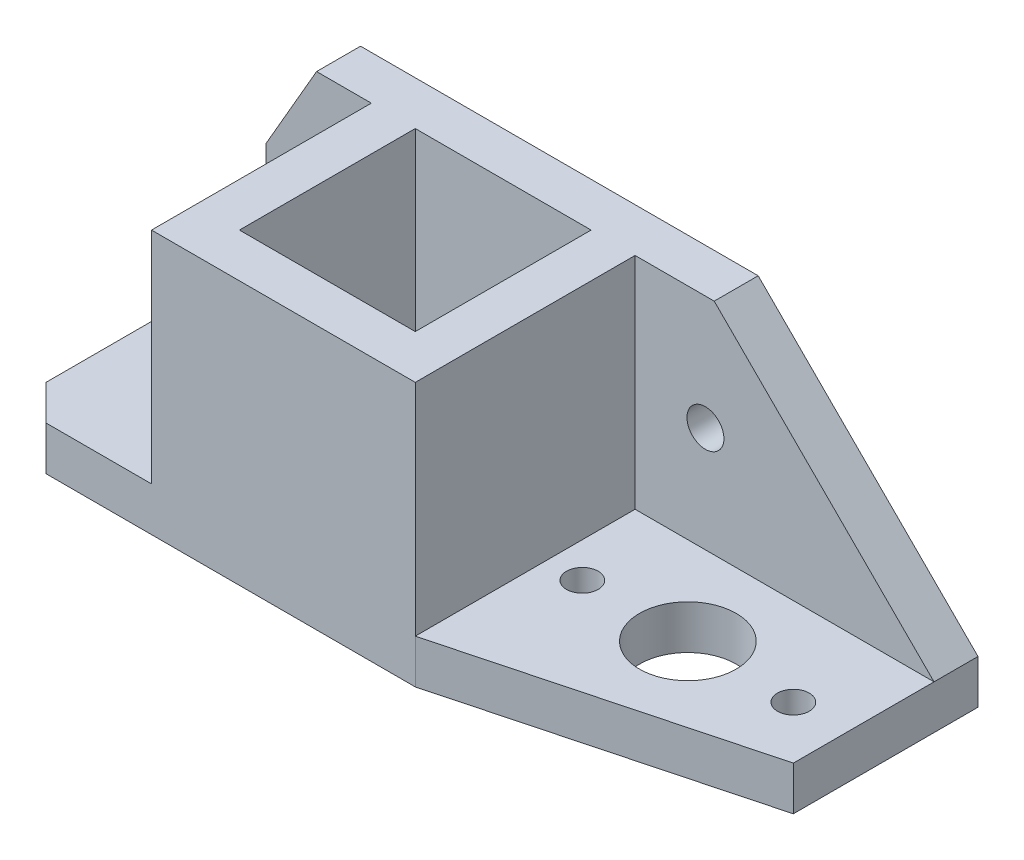
SolidWorks part; units mm, degrees
ref_plane "Front Plane" through (0, 0, 0) normal (0, 0, 1) x (1, 0, 0)
ref_plane "Top Plane" through (0, 0, 0) normal (0, 1, 0) x (1, 0, 0)
ref_plane "Right Plane" through (0, 0, 0) normal (1, 0, 0) x (0, 0, -1)
sketch "Sketch1" plane through (0, 0, 0) normal (0, 1, 0) x (1, 0, 0)
  line L1 (-15, 15) -> (15, 15)
  line L2 (-15, 15) -> (-15, -15)
  line L3 (-15, -15) -> (15, -15)
  line L4 (15, 15) -> (15, -15)
  dimension "D1" = 30
  dimension "D2" = 30
  dimension "D3" = 15
  dimension "D4" = 15
extrude "Boss-Extrude1" add sketch "Sketch1" along normal blind 30
sketch "Sketch2" plane through (0, 30, 0) normal (0, 1, 0) x (1, 0, 0)
  line L0 (-15, 15) -> (-15, -15) construction
  line L1 (-10, 10) -> (10, 10)
  line L2 (-10, 10) -> (-10, -10)
  line L3 (-10, -10) -> (10, -10)
  line L4 (10, 10) -> (10, -10)
  line L5 (15, 15) -> (-15, 15) construction
  dimension "D1" = 20
  dimension "D2" = 20
  dimension "D3" = 5
  dimension "D4" = 5
extrude "Cut-Extrude1" cut sketch "Sketch2" against normal through all
sketch "Sketch3" plane through (15, 0, 0) normal (1, 0, 0) x (0, 0, -1)
  line L0 (15, 30) -> (15, 0) construction
  line L1 (-15, 0) -> (15, 0)
  line L2 (-15, 0) -> (-15, 5)
  line L3 (-15, 5) -> (15, 5)
  line L4 (15, 0) -> (15, 5)
  dimension "D1" = 5
extrude "Boss-Extrude2" add sketch "Sketch3" along normal blind 40
sketch "Sketch4" plane through (0, 0, 0) normal (0, -1, 0) x (1, 0, 0)
  line L0 (10, 10) -> (10, -10) construction
  line L1 (-10, 10) -> (10, 10) construction
  circle A0 centre (31, 0) radius 5.5
  circle A1 centre (19, 0) radius 1.8
  circle A2 centre (43, 0) radius 1.8
  dimension "D2" = 11
  dimension "D3" = 3.6
  dimension "D4" = 3.6
  dimension "D1" = 21
  dimension "D5" = 10
  dimension "D6" = 10
  dimension "D7" = 10
  dimension "D8" = 12
  dimension "D9" = 12
extrude "Cut-Extrude2" cut sketch "Sketch4" against normal through all
sketch "Sketch7" plane through (0, 5, 0) normal (0, 1, 0) x (1, 0, 0)
  line L0 (15, -15) -> (49, -6)
  line L1 (49, -6) -> (49, 15)
  line L2 (55, 15) -> (15, 15) construction
  line L3 (49, 15) -> (55, 15)
  line L4 (55, 15) -> (55, -15)
  line L5 (55, 15) -> (55, -15) construction
  line L6 (55, -15) -> (15, -15) construction
  line L7 (55, -15) -> (15, -15)
  circle A0 centre (43, 0) radius 1.8 construction
  dimension "D1" = 6
  dimension "D2" = 6
extrude "Cut-Extrude3" cut sketch "Sketch7" against normal through all
sketch "Sketch5" plane through (15, 0, 0) normal (1, 0, 0) x (0, 0, -1)
  line L0 (15, 5) -> (-15, 5) construction
  line L1 (15, 30) -> (10, 30)
  line L2 (15, 30) -> (15, 5)
  line L3 (15, 5) -> (10, 5)
  line L4 (10, 30) -> (10, 5)
  dimension "D1" = 5
extrude "Boss-Extrude4" add sketch "Sketch5" along normal up to surface (34 mm away) up to face at (49, 2.5, -4.5)
chamfer "Chamfer1" distance 25 angle 45 1 edges at (49, 30, -12.5)
sketch "Sketch8" plane through (0, 0, -10) normal (0, 0, 1) x (1, 0, 0)
  line L0 (15, 30) -> (15, 5) construction
  line L1 (24, 30) -> (15, 30) construction
  circle A0 centre (23, 17) radius 2.1
  dimension "D1" = 4.2
  dimension "D2" = 8
  dimension "D3" = 13
extrude "Cut-Extrude4" cut sketch "Sketch8" against normal through all
sketch "Sketch9" plane through (-15, 0, 0) normal (-1, 0, 0) x (0, 0, 1)
  line L0 (-15, 0) -> (15, 0) construction
  line L1 (-15, 30) -> (-10, 30)
  line L2 (-15, 30) -> (-15, 0)
  line L3 (-15, 0) -> (-10, 0)
  line L4 (-10, 30) -> (-10, 0)
  dimension "D1" = 5
extrude "Boss-Extrude5" add sketch "Sketch9" along normal blind 12
chamfer "Chamfer2" distance 10 angle 30 1 edges at (-27, 30, -12.5) first distance on face at (-27, 15, -12.5)
sketch "Sketch10" plane through (0, 0, -10) normal (0, 0, 1) x (1, 0, 0)
  line L0 (-21.2265, 30) -> (-15, 30) construction
  line L1 (-15, 0) -> (-15, 30) construction
  circle A0 centre (-21, 17) radius 2.1
  dimension "D1" = 4.2
  dimension "D2" = 13
  dimension "D3" = 6
extrude "Cut-Extrude5" cut sketch "Sketch10" against normal through all
sketch "Sketch11" plane through (-15, 0, 0) normal (-1, 0, 0) x (0, 0, 1)
  line L0 (-10, 0) -> (-10, 30) construction
  line L1 (15, 0) -> (-10, 0)
  line L2 (15, 0) -> (15, 5)
  line L3 (15, 5) -> (-10, 5)
  line L4 (-10, 0) -> (-10, 5)
  dimension "D1" = 5
extrude "Boss-Extrude6" add sketch "Sketch11" along normal blind 16
chamfer "Chamfer3" distance 4 angle 45 2 edges at (-31, 2.5, 15) (-31, 2.5, -10)
sketch "Sketch12" plane through (0, 5, 0) normal (0, 1, 0) x (1, 0, 0)
  line L0 (-27, 10) -> (-15, 10) construction
  line L1 (-31, -11) -> (-31, 6) construction
  circle A0 centre (-25, 0) radius 1.8
  dimension "D1" = 3.6
  dimension "D2" = 10
  dimension "D3" = 6
extrude "Cut-Extrude6" cut sketch "Sketch12" against normal through all
sketch "Sketch13" plane through (0, 5, 0) normal (0, 1, 0) x (1, 0, 0)
  line L1 (-25, -3.4641) -> (-22, -1.7321)
  line L2 (-22, -1.7321) -> (-22, 1.7321)
  line L3 (-22, 1.7321) -> (-25, 3.4641)
  line L4 (-25, 3.4641) -> (-28, 1.7321)
  line L5 (-28, 1.7321) -> (-28, -1.7321)
  line L6 (-28, -1.7321) -> (-25, -3.4641)
  circle A0 centre (-25, 0) radius 3 construction
  dimension "D1" = 6
extrude "Cut-Extrude7" cut sketch "Sketch13" against normal blind 3
